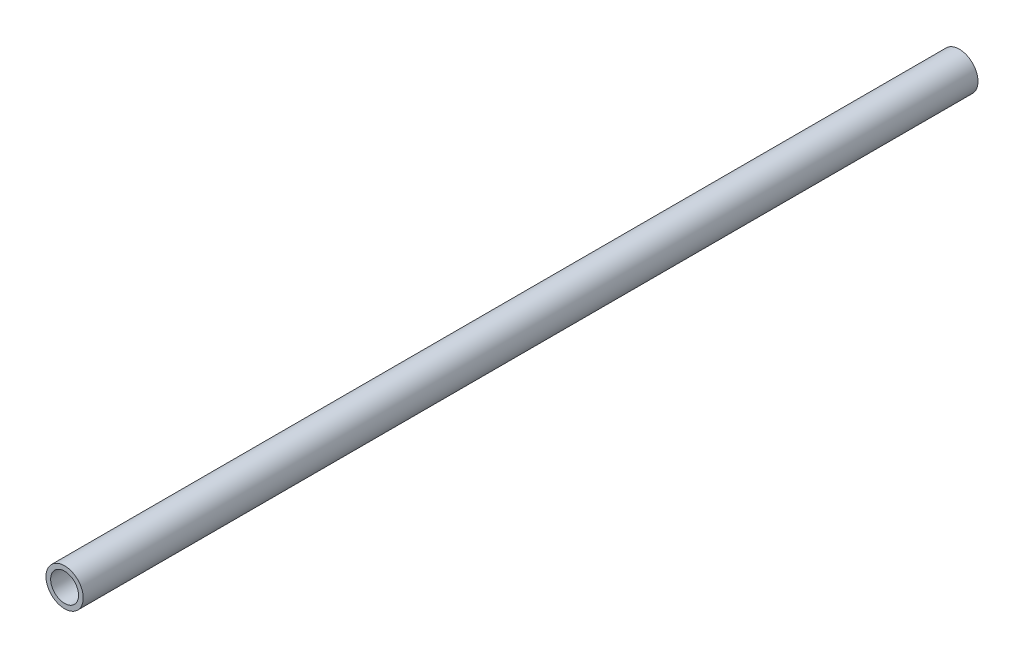
SolidWorks part; units mm, degrees
material "PC High Viscosity"
ref_plane "Front Plane" through (0, 0, 0) normal (0, 0, 1) x (1, 0, 0)
ref_plane "Top Plane" through (0, 0, 0) normal (0, 1, 0) x (1, 0, 0)
ref_plane "Right Plane" through (0, 0, 0) normal (1, 0, 0) x (0, 0, -1)
sketch "Sketch2" plane through (0, 0, 0) normal (0, 0, 1) x (1, 0, 0)
  circle A0 centre (0, 0) radius 9.525
  circle A1 centre (0, 0) radius 12.7
  dimension "D1" = 25.4
  dimension "D2" = 19.05
extrude "Boss-Extrude1" add sketch "Sketch2" along normal mid plane 610.0496
